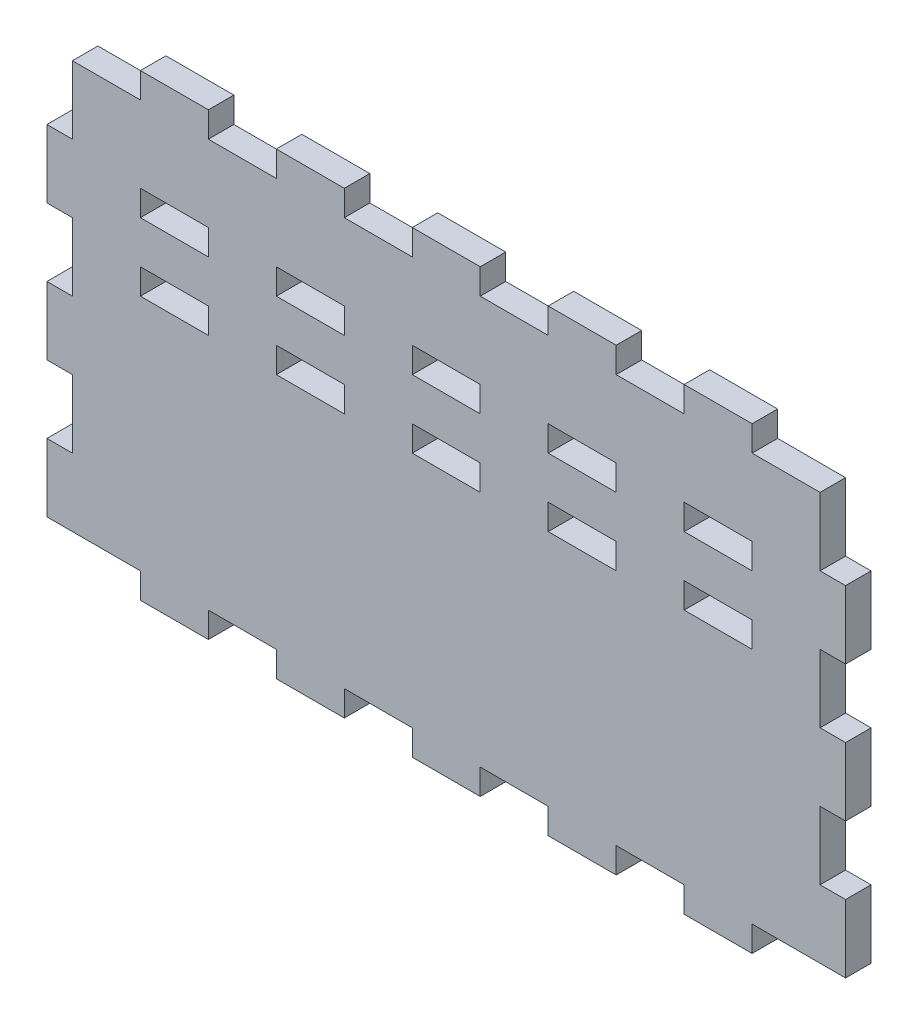
SolidWorks part; units mm, degrees
ref_plane "Front Plane" through (0, 0, 0) normal (0, 0, 1) x (1, 0, 0)
ref_plane "Top Plane" through (0, 0, 0) normal (0, 1, 0) x (1, 0, 0)
ref_plane "Right Plane" through (0, 0, 0) normal (1, 0, 0) x (0, 0, -1)
sketch "Sketch1" plane through (0, 0, 0) normal (0, 0, 1) x (1, 0, 0)
  line L1 (-139.7, -76.2) -> (139.7, -76.2)
  line L2 (-139.7, -76.2) -> (-139.7, 76.2)
  line L3 (-139.7, 76.2) -> (139.7, 76.2)
  line L4 (139.7, -76.2) -> (139.7, 76.2)
  line L5 (-139.7, -76.2) -> (139.7, 76.2) construction
  line L6 (-139.7, 76.2) -> (139.7, -76.2) construction
  point P0 (0, 0)
  dimension "D1" = 279.4
  dimension "D2" = 152.4
extrude "Boss-Extrude1" add sketch "Sketch1" along normal blind 9.525
sketch "Sketch2" plane through (0, -76.2, 0) normal (0, -1, 0) x (1, 0, 0)
  line L0 (-139.7, 0) -> (139.7, 0) construction
  line L1 (-114.3, 0) -> (-88.9, 0)
  line L2 (-114.3, 0) -> (-114.3, 9.525)
  line L3 (-114.3, 9.525) -> (-88.9, 9.525)
  line L4 (-88.9, 0) -> (-88.9, 9.525)
  line L5 (-139.7, 9.525) -> (139.7, 9.525) construction
  line L6 (-139.7, 9.525) -> (-139.7, 0) construction
  dimension "D1" = 25.4
  dimension "D2" = 25.4
extrude "Boss-Extrude2" add sketch "Sketch2" along normal blind 9.525
pattern_linear "LPattern1" count 5 spacing 50.8 along (1, 0, 0) of "Boss-Extrude2"
mirror "Mirror1" about plane through (0, 0, 0) normal (0, 1, 0) of "LPattern1"
sketch "Sketch3" plane through (139.7, 0, 0) normal (1, 0, 0) x (0, 0, -1)
  line L0 (0, 94.2975) -> (0, -94.2975) construction
  line L1 (-9.525, -76.2) -> (0, -76.2)
  line L2 (-9.525, -76.2) -> (-9.525, -50.8)
  line L3 (-9.525, -50.8) -> (0, -50.8)
  line L4 (0, -76.2) -> (0, -50.8)
  dimension "D1" = 25.4
extrude "Boss-Extrude3" add sketch "Sketch3" along normal blind 9.525
pattern_linear "LPattern2" count 3 spacing 50.8 along (0, 1, 0) of "Boss-Extrude3"
mirror "Mirror2" about plane through (0, 0, 0) normal (1, 0, 0) of "LPattern2"
sketch "Sketch4" plane through (0, 0, 9.525) normal (0, 0, 1) x (1, 0, 0)
  line L0 (-139.7, 25.4) -> (-139.7, 0) construction
  line L1 (-88.9, 12.7) -> (-114.3, 12.7)
  line L2 (-88.9, 12.7) -> (-88.9, 22.225)
  line L3 (-88.9, 22.225) -> (-114.3, 22.225)
  line L4 (-114.3, 12.7) -> (-114.3, 22.225)
  line L5 (-88.9, -76.2) -> (-63.5, -76.2) construction
  line L7 (-114.3, 38.1) -> (-88.9, 38.1)
  line L8 (-114.3, 38.1) -> (-114.3, 47.625)
  line L9 (-114.3, 47.625) -> (-88.9, 47.625)
  line L10 (-88.9, 38.1) -> (-88.9, 47.625)
  point P8 (-76.2, -76.2)
  dimension "D1" = 25.4
  dimension "D2" = 9.525
  dimension "D3" = 25.4
  dimension "D4" = 88.9
  dimension "D5" = 9.525
  dimension "D6" = 25.4
  dimension "D7" = 114.3
extrude "Cut-Extrude1" cut sketch "Sketch4" against normal through all
pattern_linear "LPattern3" count 5 spacing 50.8 along (1, 0, 0) of "Cut-Extrude1"
